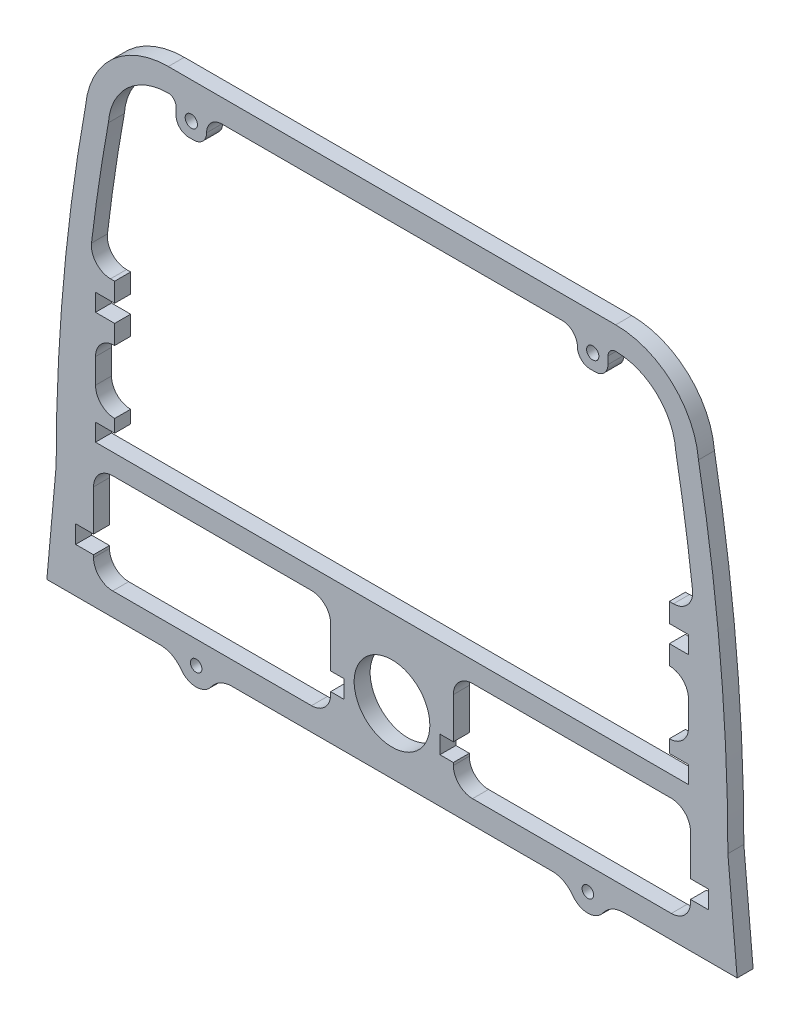
SolidWorks part; units mm, degrees
material "Delrin 2700 NC010, Low Viscosity Acetal Copolymer (SS)"
ref_plane "Front Plane" through (0, 0, 0) normal (0, 0, 1) x (1, 0, 0)
ref_plane "Top Plane" through (0, 0, 0) normal (0, 1, 0) x (1, 0, 0)
ref_plane "Right Plane" through (0, 0, 0) normal (1, 0, 0) x (0, 0, -1)
sketch "Sketch1" plane through (0, 0, 0) normal (0, 0, 1) x (1, 0, 0)
  line L0 (33.3676, -11.9888) -> (34.29, -22.225)
  line L1 (22.225, 27.94) -> (-22.225, 27.94)
  line L2 (-34.29, -22.225) -> (-30.4467, 20.4259) construction
  line L3 (-33.3676, -11.9888) -> (-33.3676, 14.6458) construction
  line L4 (-33.3676, -11.9888) -> (-34.29, -22.225)
  line L5 (16.9079, 25.654) -> (-16.9079, 25.654)
  line L6 (6.096, -17.78) -> (6.096, -19.939)
  line L7 (-29.6529, -19.939) -> (-6.096, -19.939)
  line L8 (-34.29, -22.225) -> (-21.299, -22.225)
  line L9 (-29.6529, -10.033) -> (-29.6529, -16.002)
  line L10 (18.4213, 24.1407) -> (18.4213, 24.1363)
  line L11 (19.6913, 22.8663) -> (20.1867, 22.8663)
  line L12 (21.4567, 24.1363) -> (21.4567, 24.8713)
  line L13 (-21.4567, 24.1363) -> (-21.4567, 24.8713)
  line L14 (-19.6913, 22.8663) -> (-20.1867, 22.8663)
  line L15 (-18.4213, 24.1407) -> (-18.4213, 24.1363)
  line L16 (29.4572, -8.001) -> (-29.4572, -8.001)
  line L17 (29.6529, -10.033) -> (6.096, -10.033)
  line L18 (0, 18.415) -> (0, -18.415) construction
  line L19 (-1007.9925, 0) -> (48992.0075, 0) construction
  line L20 (-6.096, -10.033) -> (-29.6529, -10.033)
  line L21 (19.939, 24.384) -> (21.4567, 24.384) construction
  line L22 (6.096, -19.939) -> (29.6529, -19.939)
  line L23 (-6.096, -10.033) -> (-6.096, -16.002)
  line L24 (5.9491, -2.2098) -> (59.5431, -2.2098) construction
  line L25 (5.9491, -2.2098) -> (5.9491, -11.9888) construction
  line L26 (3.4091, -11.9888) -> (-3.4091, -11.9888) construction
  line L27 (59.5431, -2.2098) -> (59.5431, -11.9888) construction
  line L28 (-31.7887, -19.939) -> (31.7887, -19.939) construction
  line L29 (22.225, 25.654) -> (-22.225, 25.654) construction
  line L30 (-6.096, -19.939) -> (-6.1666, -19.9899)
  line L31 (29.4572, -6.2738) -> (27.5522, -6.2738)
  line L32 (27.5522, -6.2738) -> (27.5522, -5.0038)
  line L33 (-29.6529, -16.002) -> (-31.4309, -16.002)
  line L34 (27.5522, -5.0038) -> (29.4572, -5.0038)
  line L35 (29.4572, 1.27) -> (27.5522, 1.27)
  line L36 (27.5522, 1.27) -> (27.5522, 3.175)
  line L37 (27.5522, 3.175) -> (29.4572, 3.175)
  line L38 (29.4572, 4.9022) -> (27.5522, 4.9022)
  line L39 (19.939, 24.384) -> (18.4213, 24.384) construction
  line L40 (27.5522, 4.9022) -> (27.5522, 6.8072)
  line L41 (27.5522, 6.8072) -> (30.0922, 6.8072)
  line L42 (19.939, 24.384) -> (19.939, 22.8663) construction
  line L43 (6.096, -10.033) -> (6.096, -16.002)
  line L44 (-29.4572, -6.2738) -> (-29.4572, -8.001)
  line L45 (-29.4572, -6.2738) -> (-27.5522, -6.2738)
  line L46 (-27.5522, -6.2738) -> (-27.5522, -5.0038)
  line L47 (-27.5522, -5.0038) -> (-29.4572, -5.0038)
  line L48 (-29.4572, 1.27) -> (-29.4572, -5.0038)
  line L49 (-29.4572, 1.27) -> (-27.5522, 1.27)
  line L50 (-27.5522, 1.27) -> (-27.5522, 3.175)
  line L51 (-27.5522, 3.175) -> (-29.4572, 3.175)
  line L52 (-29.4572, 4.9022) -> (-29.4572, 3.175)
  line L53 (-31.4309, -16.002) -> (-31.4309, -17.78)
  line L54 (-31.4309, -17.78) -> (-29.6529, -17.78)
  line L55 (-6.096, -16.002) -> (-4.7609, -16.002)
  line L56 (-4.7609, -16.002) -> (-4.7609, -17.78)
  line L57 (-4.7609, -17.78) -> (-6.096, -17.78)
  line L58 (-29.6529, -10.033) -> (-29.6529, -19.939) construction
  line L59 (-29.6529, -14.986) -> (-33.4249, -14.986) construction
  line L60 (-29.6529, -14.986) -> (-0.4824, -14.986) construction
  line L61 (-6.096, -17.78) -> (-6.096, -19.939)
  line L62 (-29.6529, -19.939) -> (-29.6529, -17.78)
  line L63 (29.6529, -19.939) -> (29.6529, -17.78)
  line L64 (-31.0816, -12.0913) -> (-31.7887, -19.939) construction
  line L65 (29.6529, -10.033) -> (29.6529, -16.002)
  line L66 (31.4309, -17.78) -> (29.6529, -17.78)
  line L67 (31.4309, -16.002) -> (31.4309, -17.78)
  line L68 (29.6529, -16.002) -> (31.4309, -16.002)
  line L69 (6.096, -16.002) -> (4.7609, -16.002)
  line L70 (4.7609, -16.002) -> (4.7609, -17.78)
  line L71 (4.7609, -17.78) -> (6.096, -17.78)
  line L72 (29.4572, 4.9022) -> (29.4572, 3.175)
  line L73 (31.0816, -12.0913) -> (31.7887, -19.939) construction
  line L74 (29.4572, 1.27) -> (29.4572, -5.0038)
  line L75 (29.4572, -6.2738) -> (29.4572, -8.001)
  line L76 (-29.4572, 4.9022) -> (-27.5522, 4.9022)
  line L77 (-27.5522, 4.9022) -> (-27.5522, 6.8072)
  line L78 (-27.5522, 6.8072) -> (-30.0922, 6.8072)
  line L79 (-17.616, -22.225) -> (17.616, -22.225)
  line L80 (21.299, -22.225) -> (34.29, -22.225)
  line L81 (-34.29, -22.225) -> (34.29, -22.225) construction
  arc A0 (22.225, 27.94) -> (30.4467, 20.4259) centre (22.225, 19.685) cw
  arc A1 (-22.225, 27.94) -> (-30.4467, 20.4259) centre (-22.225, 19.685) ccw
  arc A2 (33.3676, -11.9888) -> (30.4467, 20.4259) centre (-147.9525, -11.9888) ccw
  circle A3 centre (0, -15.748) radius 3.7592
  circle A4 centre (19.4575, -22.225) radius 0.5715
  arc A5 (-33.3676, -11.9888) -> (-30.4467, 20.4259) centre (147.9525, -11.9888) cw
  arc A6 (-17.616, -22.225) -> (-21.299, -22.225) centre (-19.4575, -22.225) cw
  arc A7 (17.616, -22.225) -> (21.299, -22.225) centre (19.4575, -22.225) ccw
  arc A8 (20.1867, 22.8663) -> (21.4567, 24.1363) centre (20.1867, 24.1363) ccw
  circle A9 centre (-19.939, 24.384) radius 0.6096
  circle A10 centre (19.939, 24.384) radius 0.6096
  arc A11 (18.4213, 24.1363) -> (19.6913, 22.8663) centre (19.6913, 24.1363) ccw
  circle A12 centre (-19.4575, -22.225) radius 0.5715
  arc A13 (18.4213, 24.1407) -> (16.9079, 25.654) centre (16.9079, 24.1407) ccw
  arc A14 (22.2416, 25.654) -> (21.4567, 24.8713) centre (22.2394, 24.8713) ccw
  arc A15 (-22.2416, 25.654) -> (-21.4567, 24.8713) centre (-22.2394, 24.8713) cw
  arc A16 (-20.1867, 22.8663) -> (-21.4567, 24.1363) centre (-20.1867, 24.1363) cw
  arc A17 (-18.4213, 24.1363) -> (-19.6913, 22.8663) centre (-19.6913, 24.1363) cw
  arc A18 (-22.2416, 25.654) -> (-28.1777, 20.1262) centre (-22.225, 19.685) ccw
  arc A19 (-18.4213, 24.1407) -> (-16.9079, 25.654) centre (-16.9079, 24.1407) cw
  arc A20 (31.0816, -12.0913) -> (31.0816, -11.9888) centre (-147.9525, -11.9888) ccw
  circle A21 centre (-19.4575, -22.225) radius 1.8415 construction
  arc A23 (22.2416, 25.654) -> (28.1777, 20.1262) centre (22.225, 19.685) cw
  arc A25 (-22.225, 25.654) -> (-28.1777, 20.1262) centre (-22.225, 19.685) ccw construction
  arc A26 (22.225, 25.654) -> (28.1777, 20.1262) centre (22.225, 19.685) cw construction
  arc A28 (-31.0816, -12.0913) -> (-28.1777, 20.1262) centre (147.9525, -11.9888) cw construction
  arc A30 (31.0816, -12.0913) -> (28.1777, 20.1262) centre (-147.9525, -11.9888) ccw construction
  arc A31 (30.0922, 6.8072) -> (28.1777, 20.1262) centre (-147.9525, -11.9888) ccw
  arc A33 (-30.0922, 6.8072) -> (-28.1777, 20.1262) centre (147.9525, -11.9888) cw
  point P0 (0, 0)
  point P1 (0, 27.94)
  point P31 (0, -11.9888)
  point P121 (-30.9018, -14.986)
  point P135 (-17.616, -22.225)
  dimension "D4" = 2.286
  dimension "D6" = 8.255
  dimension "D7" = 19.4575
  dimension "D8" = 50.165
  dimension "D9" = 15.748
  dimension "D5" = 1.2192
  dimension "D17" = 1.143
  dimension "D3" = 7.5184
  dimension "D18" = 1.27
  dimension "D19" = 1.27
  dimension "D26" = 11.176
  dimension "D28" = 0.7827
  dimension "D29" = 1.5133
  dimension "D32" = 1.778
  dimension "D2" = 44.45
  dimension "D10" = 1.27
  dimension "D11" = 1.27
  dimension "D12" = 68.58
  dimension "D13" = 19.939
  dimension "D14" = 22.225
  dimension "D15" = 53.594
  dimension "D16" = 9.779
  dimension "D20" = 6.096
  dimension "D21" = 11.938
  dimension "D22" = 2.032
  dimension "D23" = 1.7272
  dimension "D24" = 1.27
  dimension "D25" = 1.905
  dimension "D27" = 0.4954
  dimension "D30" = 1.905
  dimension "D31" = 1.7272
  dimension "D33" = 1.778
  dimension "D34" = 2.159
  dimension "D35" = 23.5569
  dimension "D36" = 26.67
  dimension "D37" = 1.905
  dimension "D38" = 2.54
extrude "Boss-Extrude1" add sketch "Sketch1" along normal blind 1.5875 contours L8 A12 A4 L0 A2 A0 L1 A1 A5 L4 L74 L16 A18 A15 L13 A16 L14 A17 L15 A19 L5 A13 L10 A11 L11 A8 L12 A14 A23 A20 L22 L43 L17 A10 A9 A3 L20 region at (32.9716, -17.1841, 0)
ref_axis "Axis1" through (0, -15.748, 0) along (0, 0, 1)
fillet "Fillet1" radius 1.905 8 edges at (-6.096, -10.033, 0.7937) (6.096, -10.033, 0.7937) (-6.096, -19.939, 0.7937) (-29.6529, -19.939, 0.7937) (-29.6529, -10.033, 0.7937) (6.096, -19.939, 0.7937) (29.6529, -19.939, 0.7937) (29.6529, -10.033, 0.7937)
fillet "Fillet2" radius 1.905 6 edges at (-29.4572, 1.27, 0.7937) (-29.4572, -5.0038, 0.7937) (-30.0922, 6.8072, 0.7937) (29.4572, -5.0038, 0.7937) (29.4572, 1.27, 0.7937) (30.0922, 6.8072, 0.7937)
fillet "Fillet3" radius 2.54 4 edges at (-17.616, -22.225, 0.7937) (-21.299, -22.225, 0.7937) (17.616, -22.225, 0.7937) (21.299, -22.225, 0.7937)
